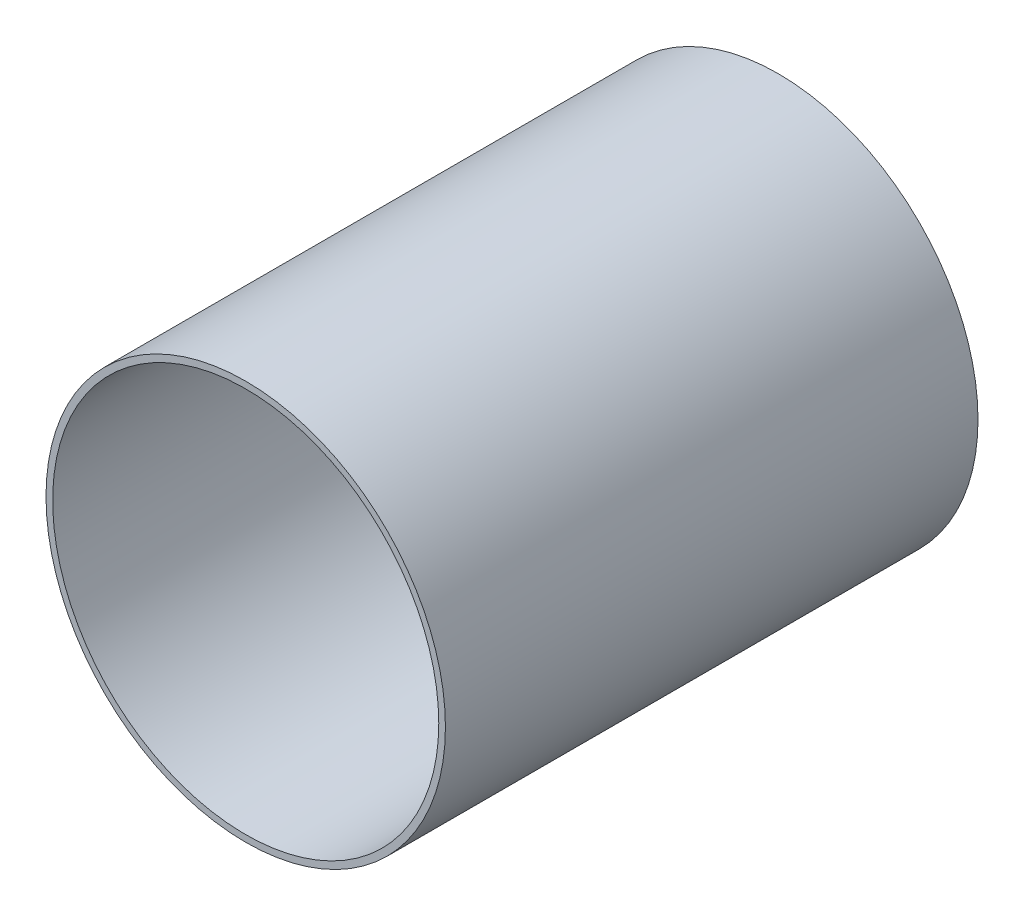
SolidWorks part; units mm, degrees
ref_plane "Front Plane" through (0, 0, 0) normal (0, 0, 1) x (1, 0, 0)
ref_plane "Top Plane" through (0, 0, 0) normal (0, 1, 0) x (1, 0, 0)
ref_plane "Right Plane" through (0, 0, 0) normal (1, 0, 0) x (0, 0, -1)
sketch "Sketch1" plane through (0, 0, 0) normal (0, 0, 1) x (1, 0, 0)
  circle A0 centre (0, 0) radius 45
  circle A1 centre (0, 0) radius 43.5
  dimension "D1" = 90
  dimension "D2" = 87
extrude "Boss-Extrude1" add sketch "Sketch1" along normal blind 120
